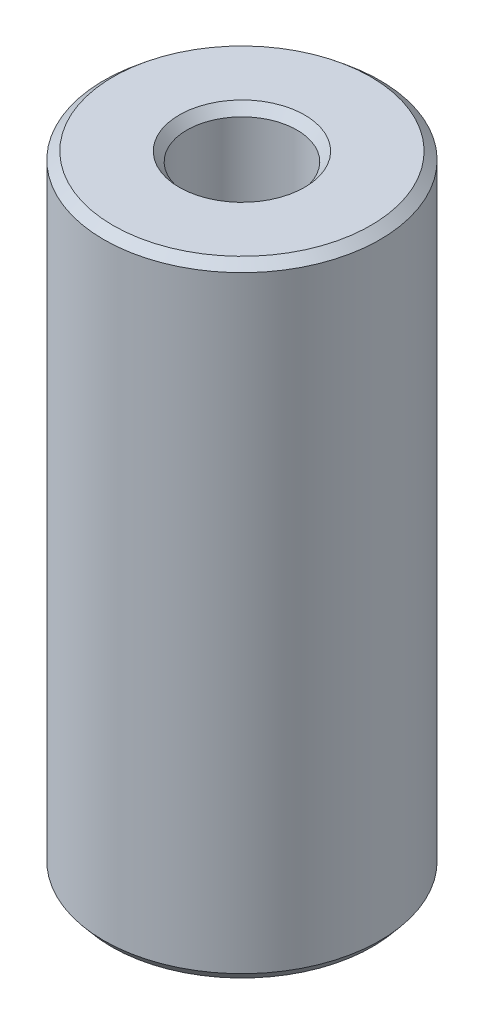
SolidWorks part; units mm, degrees
ref_plane "Front Plane" through (0, 0, 0) normal (0, 0, 1) x (1, 0, 0)
ref_plane "Top Plane" through (0, 0, 0) normal (0, 1, 0) x (1, 0, 0)
ref_plane "Right Plane" through (0, 0, 0) normal (1, 0, 0) x (0, 0, -1)
sketch "Sketch1" plane through (0, 0, 0) normal (0, 1, 0) x (1, 0, 0)
  circle A0 centre (0, 0) radius 17.5
  dimension "SLEEVE_OD" = 35
extrude "Boss-Extrude1" add sketch "Sketch1" along normal blind 79.1177
sketch "Sketch2" plane through (0, 0, 0) normal (0, 1, 0) x (1, 0, 0)
  circle A0 centre (0, 0) radius 6.9789
  dimension "BORE_D" = 13.9579
extrude "Cut-Extrude1" cut sketch "Sketch2" along normal through all
chamfer "Chamfer1" distance 0.9737 angle 50.17 4 edges at (0, 79.1177, 6.9789) (0, 0, 6.9789) (0, 0, 17.5) (0, 79.1177, 17.5) first distance on face at (0, 79.1177, 6.9789) first distance on face at (0, 0, 6.9789) first distance on face at (0, 79.1177, 17.5)
